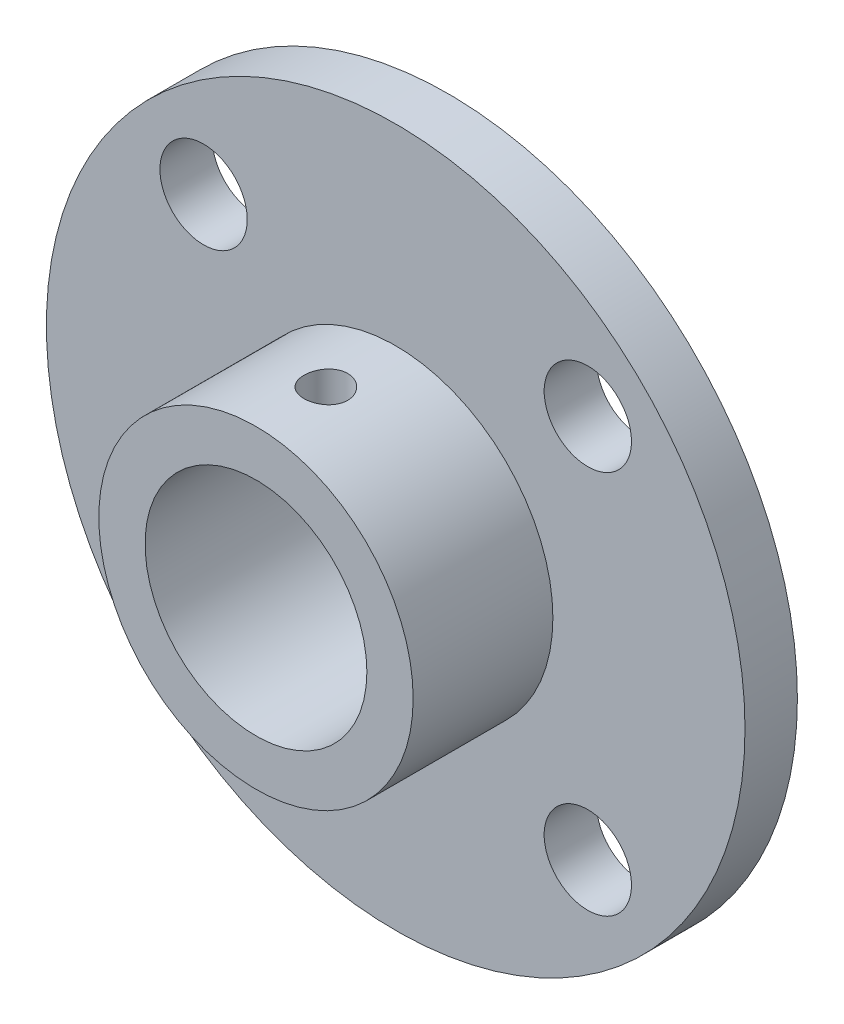
SolidWorks part; units mm, degrees
ref_plane "Front Plane" through (0, 0, 0) normal (0, 0, 1) x (1, 0, 0)
ref_plane "Top Plane" through (0, 0, 0) normal (0, 1, 0) x (1, 0, 0)
ref_plane "Right Plane" through (0, 0, 0) normal (1, 0, 0) x (0, 0, -1)
sketch "Sketch1" plane through (0, 0, 0) normal (0, 0, 1) x (1, 0, 0)
  circle A0 centre (0, 0) radius 20
  dimension "D1" = 40
extrude "Boss-Extrude1" add sketch "Sketch1" along normal blind 3
sketch "Sketch2" plane through (0, 0, 3) normal (0, 0, 1) x (1, 0, 0)
  circle A0 centre (0, 0) radius 9
  dimension "D1" = 18
extrude "Boss-Extrude2" add sketch "Sketch2" along normal blind 8
sketch "Sketch4" plane through (0, 0, 11) normal (0, 0, 1) x (1, 0, 0)
  circle A0 centre (0, 0) radius 6.35
  dimension "D1" = 12.7
extrude "Cut-Extrude1" cut sketch "Sketch4" against normal through all
ref_plane "Plane2" through (0, 0, 7) normal (0, 0, 1) x (1, 0, 0)
hole_wizard "M3 Tapped Hole1" positions "3DSketch7" profile "Sketch15" tap size "M3" standard "ISO" end condition up to next
sketch3d "3DSketch7"
  point P0 (0, 9, 7)
  dimension "D1" = 4
sketch "Sketch15" plane through (0, 9, 7) normal (1, 0, 0) x (0, 0, 1)
  line L0 (0, 0) -> (0, 2.65)
  line L1 (0, 2.65) -> (1.25, 2.65)
  line L2 (1.25, 2.65) -> (1.25, 0)
  line L5 (1.25, 0) -> (0, 0)
  line L11 (0, -6.35) -> (0, 107.95) construction
  dimension "Thru Tap Drill Dia." = 2.5
  dimension "Thru Tap Drill Depth" = 2.65
cosmetic thread "Hole Thread1" parameters "D2"=3
sketch "Sketch16" plane through (0, 0, 3) normal (0, 0, 1) x (1, 0, 0)
  line L0 (0, 0) -> (34.2865, 0) construction
  line L1 (0, 0) -> (11, 11) construction
  point P0 (11, 11)
  dimension "D1" = 11
  dimension "D2" = 45
hole_wizard "Ø5.0 (5) Diameter Hole1" positions "3DSketch8" profile "Sketch17" hole size "Ø5.0" standard "ISO" end condition through all
sketch3d "3DSketch8"
  point P0 (11, 11, 3)
sketch "Sketch17" plane through (11, 11, 3) normal (1, 0, 0) x (0, -1, 0)
  line L0 (0, 0) -> (0, 3)
  line L1 (0, 3) -> (2.5, 3)
  line L2 (2.5, 3) -> (2.5, 0)
  line L5 (2.5, 0) -> (0, 0)
  line L11 (0, -6.35) -> (0, 107.95) construction
  dimension "Thru Hole Dia." = 5
  dimension "Thru Hole Depth" = 3
pattern_circular "CirPattern1" count 4 over 360 about axis through (0, 0, 11) along (0, 0, -1) of "Ø5.0 (5) Diameter Hole1"
